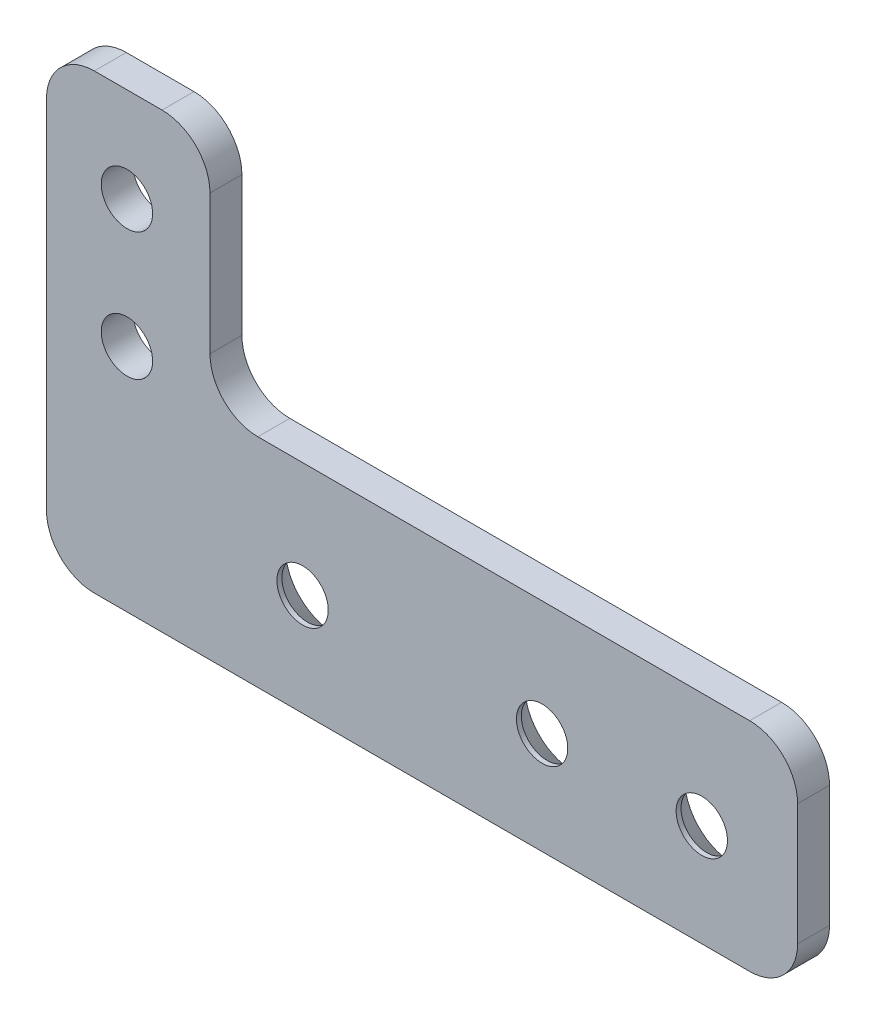
SolidWorks part; units mm, degrees
material "6061-T6 (SS)"
ref_plane "Front Plane" through (0, 0, 0) normal (0, 0, 1) x (1, 0, 0)
ref_plane "Top Plane" through (0, 0, 0) normal (0, 1, 0) x (1, 0, 0)
ref_plane "Right Plane" through (0, 0, 0) normal (1, 0, 0) x (0, 0, -1)
sketch "Sketch1" plane through (0, 0, 0) normal (0, 0, 1) x (1, 0, 0)
  line L0 (41.275, -11.049) -> (-33.401, -11.049) construction
  line L1 (-41.275, -23.749) -> (41.275, -23.749)
  line L2 (-41.275, -23.749) -> (-41.275, 23.749)
  line L3 (-41.275, 23.749) -> (41.275, 23.749)
  line L4 (41.275, -23.749) -> (41.275, 23.749)
  line L5 (-41.275, -23.749) -> (41.275, 23.749) construction
  line L6 (-41.275, 23.749) -> (41.275, -23.749) construction
  line L7 (41.275, 23.749) -> (-17.145, 23.749)
  line L8 (41.275, 23.749) -> (41.275, 0.381)
  line L9 (41.275, 0.381) -> (-17.145, 0.381)
  line L10 (-17.145, 23.749) -> (-17.145, 0.381)
  line L11 (-41.275, -23.749) -> (-33.401, -23.749)
  line L12 (-41.275, -23.749) -> (-41.275, 23.749)
  line L13 (-41.275, 23.749) -> (-33.401, 23.749)
  line L14 (-33.401, -23.749) -> (-33.401, 23.749)
  line L15 (-33.401, -23.749) -> (41.275, -23.749)
  line L16 (-33.401, -23.749) -> (-33.401, -21.209)
  line L17 (-33.401, -21.209) -> (41.275, -21.209)
  line L18 (41.275, -23.749) -> (41.275, -21.209)
  line L19 (-33.401, 23.876) -> (-17.145, 23.876) construction
  circle A0 centre (-25.4, -11.049) radius 2.5527
  circle A1 centre (-25.4, 1.651) radius 2.5527
  circle A2 centre (-25.4, 14.351) radius 2.5527
  point P0 (0, 0)
  point P22 (31.75, -11.049)
  point P23 (-7.9375, -11.049)
  point P24 (15.875, -11.049)
  dimension "D7" = 5.1054
  dimension "D1" = 82.55
  dimension "D2" = 47.498
  dimension "D3" = 24.13
  dimension "D4" = 24.13
  dimension "D5" = 7.874
  dimension "D6" = 47.498
  dimension "D8" = 17.4625
  dimension "D9" = 12.7
  dimension "D10" = 12.7
  dimension "D11" = 12.7
  dimension "D12" = 9.525
  dimension "D13" = 57.15
  dimension "D14" = 15.875
  dimension "D15" = 15.875
  dimension "D16" = 2.54
extrude "Boss-Extrude1" add sketch "Sketch1" along normal blind 3.175 contours L14 L17 L4 L9 L10 L3 A2 A1 A0 | A0 region at (-0.8769, -6.375, 0) region at (-25.4, -11.049, 0)
fillet "Fillet1" radius 4.7625 6 edges at (-33.401, 23.749, 1.5875) (-17.145, 23.749, 1.5875) (-17.145, 0.381, 1.5875) (41.275, 0.381, 1.5875) (41.275, -21.209, 1.5875) (-33.401, -21.209, 1.5875)
hole_wizard "CSK for #10 Flat Head Machine Screw3" positions "Sketch6" profile "Sketch7" countersink size "#10" standard "ANSI Inch" end condition through all
sketch "Sketch6" plane through (0, 0, 0) normal (0, 0, -1) x (-1, 0, 0)
  point P0 (-31.75, -11.049)
  point P3 (-15.875, -11.049)
  point P6 (7.9375, -11.049)
sketch "Sketch7" plane through (31.75, -11.049, 0) normal (1, 0, 0) x (0, 1, 0)
  line L0 (0, 0) -> (0, 3.175)
  line L1 (0, 3.175) -> (2.5527, 3.175)
  line L2 (2.5527, 3.175) -> (2.5527, 2.6882)
  line L3 (2.5527, 2.6882) -> (4.8895, 0)
  line L5 (4.8895, 0) -> (0, 0)
  line L6 (-2.5527, 2.6882) -> (-4.8895, 0) construction
  line L11 (0, -6.35) -> (0, 107.95) construction
  dimension "Thru Hole Dia." = 5.1054
  dimension "Thru Hole Depth" = 3.175
  dimension "Near C'Sink Dia." = 9.779
  dimension "Near C'Sink Angle" = 82
